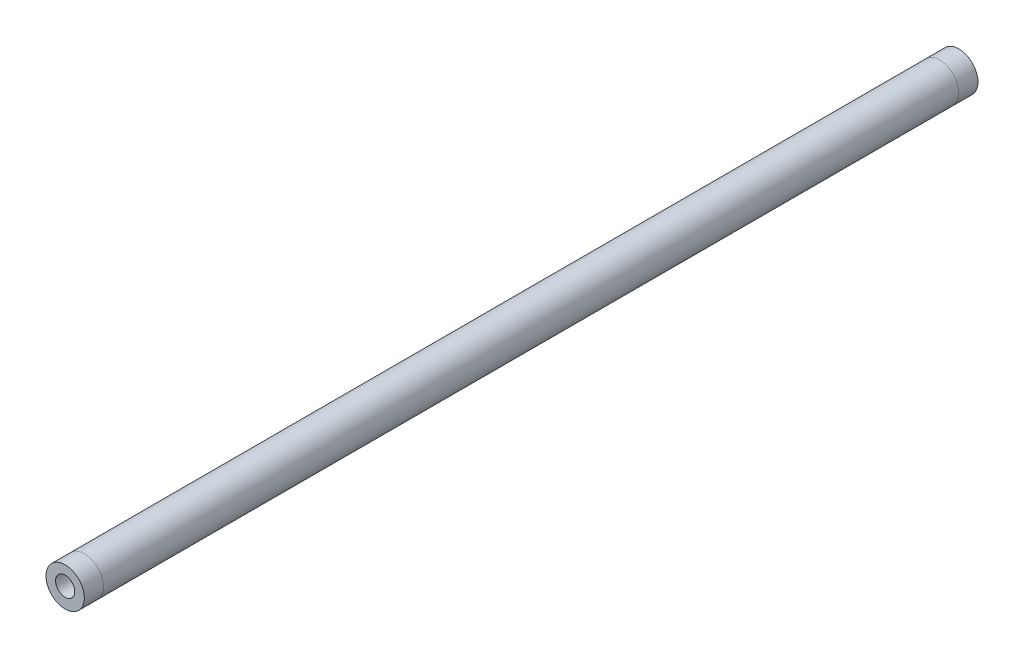
SolidWorks part; units mm, degrees
material "AISI 4130 Steel, normalized at 870C"
ref_plane "Front Plane" through (0, 0, 0) normal (0, 0, 1) x (1, 0, 0)
ref_plane "Top Plane" through (0, 0, 0) normal (0, 1, 0) x (1, 0, 0)
ref_plane "Right Plane" through (0, 0, 0) normal (1, 0, 0) x (0, 0, -1)
sketch "Axis" plane through (0, 0, 0) normal (0, 1, 0) x (1, 0, 0)
  line L0 (0, 0) -> (0, 21.8948) construction
  line L1 (0, 21.8948) -> (0, 317.7138) construction
  line L2 (0, 317.7138) -> (0, 339.6086) construction
  dimension "D1" = 21.8948
  dimension "D2" = 339.6086
sketch "Sketch2" plane through (0, 0, 0) normal (0, 0, 1) x (1, 0, 0)
  circle A0 centre (0, 0) radius 6.35
  circle A1 centre (0, 0.235) radius 3.175
  circle A2 centre (0, 0) radius 4.7625
  dimension "D1" = 12.7
  dimension "D2" = 6.35
  dimension "D3" = 9.525
extrude "Threaded Insert 1-1" add sketch "Sketch2" against normal blind 6.35 from vertex contours A0 A2 | A2 A1 region at (-6.1704, 0, 0) region at (-4.6278, 0, 0) starting at point (0, 0, -21.8948)
extrude "Threaded Insert 1-2" add sketch "Sketch2<5>" against normal blind 6.35 from surface contours A2 A1 region at (-4.6278, 0, 0) starting at face at (6.35, 0, -28.2448)
sketch "Sketch2<5>" plane through (0, 0, 0) normal (0, 0, 1) x (1, 0, 0) same geometry as "Sketch2"
extrude "Boss-Extrude4" add sketch "Sketch2<7>" along normal blind 6.35 from vertex separate body contours A0 A2 | A2 A1 region at (-6.1704, 0, 0) region at (-4.6278, 0, 0) starting at point (0, 0, -317.7138)
sketch "Sketch2<7>" plane through (0, 0, 0) normal (0, 0, 1) x (1, 0, 0) same geometry as "Sketch2"
extrude "Boss-Extrude5" add sketch "Sketch2<8>" along normal blind 6.35 from surface contours A2 A1 region at (-4.6278, 0, 0) starting at face at (6.35, 0, -311.3638)
sketch "Sketch2<8>" plane through (0, 0, 0) normal (0, 0, 1) x (1, 0, 0) same geometry as "Sketch2"
extrude "Boss-Extrude6" add sketch "Sketch2<9>" against normal up to surface (311.3638 mm away) from surface separate body contours A0 A2 region at (-6.1704, 0, 0) up to face at (6.35, 0, -311.3638) starting at face at (4.7625, 0, -28.2448)
sketch "Sketch2<9>" plane through (0, 0, 0) normal (0, 0, 1) x (1, 0, 0) same geometry as "Sketch2"
equation "\"Tube Outer Diameter\"= .5"
equation "\"Tube Inner Diameter\"= .375"
equation "\"Rod end Diameter\"= .25"
equation "\"Threaded Insert Out\"= .25"
equation "\"Threaded Insert In\"= .25'`"
equation "\"D1@Sketch2\"=\"Tube Outer Diameter\""
equation "\"D2@Sketch2\"=\"Rod end Diameter\""
equation "\"D1@Threaded Insert 1-1\" = \"Threaded Insert Out\""
equation "\"D3@Sketch2\"=\"Tube Inner Diameter\""
equation "\"D1@Threaded Insert 1-2\" = \"Threaded Insert In\""
equation "\"D1@Boss-Extrude4\"=\"Threaded Insert Out\""
equation "\"D1@Boss-Extrude5\"=\"Threaded Insert In\""
